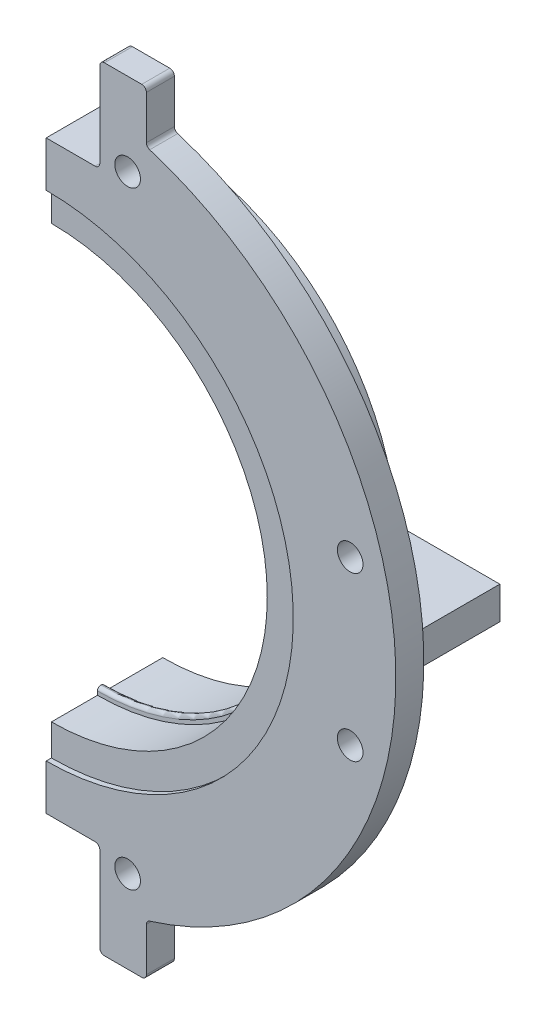
SolidWorks part; units mm, degrees
ref_plane "Front" through (0, 0, 0) normal (0, 0, 1) x (1, 0, 0)
ref_plane "Top" through (0, 0, 0) normal (0, 1, 0) x (1, 0, 0)
ref_plane "Right" through (0, 0, 0) normal (1, 0, 0) x (0, 0, -1)
sketch "Sketch1" plane through (0, 0, 0) normal (0, 0, 1) x (1, 0, 0)
  line L1 (0, 0) -> (180, 0)
  line L2 (0, 0) -> (0, 180)
  line L3 (0, 180) -> (180, 180)
  line L4 (180, 0) -> (180, 180)
  dimension "D1" = 180
extrude "Boss-Extrude1" add sketch "Sketch1" along normal blind 6
sketch "Sketch2" plane through (0, 0, 0) normal (0, 0, -1) x (-1, 0, 0)
  line L0 (0, 90) -> (-180, 90) construction
  line L1 (0, 180) -> (0, 0) construction
  line L3 (-180, 0) -> (-180, 180) construction
  circle A0 centre (-90, 90) radius 46.3
  circle A1 centre (-90, 90) radius 50.3
  point P11 (-90, 90)
  dimension "D1" = 92.6
  dimension "D2" = 4
extrude "Boss-Extrude2" add sketch "Sketch2" along normal blind 19
sketch "Sketch3" plane through (0, 0, 0) normal (0, 0, -1) x (-1, 0, 0)
  circle A0 centre (-90, 90) radius 46.3
  dimension "D1" = 92.6
extrude "Cut-Extrude1" cut sketch "Sketch3" against normal up to next
sketch "Sketch4" plane through (0, 0, 0) normal (0, 0, -1) x (-1, 0, 0)
  line L0 (0, 77.5) -> (0, 102.5)
  line L1 (0, 180) -> (0, 0) construction
  line L2 (0, 77.5) -> (-41.2779, 77.5)
  line L3 (0, 102.5) -> (-41.2779, 102.5)
  circle A0 centre (-90, 90) radius 50.3 construction
  arc A1 (-41.2779, 77.5) -> (-41.2779, 102.5) centre (-90, 90) ccw
  point P2 (0, 90)
  point P5 (0, 90)
  dimension "D1" = 25
extrude "Boss-Extrude3" add sketch "Sketch4" along normal blind 60
ref_plane "Plane1" through (0, 90, 0) normal (0, -1, 0) x (-1, 0, 0)
sketch "Sketch7" plane through (0, 0, 0) normal (0, 0, -1) x (-1, 0, 0)
  circle A0 centre (-90, 90) radius 46.3 construction
  circle A1 centre (-90, 90) radius 46.3 construction
  circle A2 centre (-90, 90) radius 46.3
  circle A3 centre (-90, 90) radius 46.3
sketch "Sketch6" plane through (0, 90, 0) normal (0, -1, 0) x (-1, 0, 0)
  line L0 (-51.2779, -3.75) -> (-40, -3.75)
  line L1 (-40, -3.75) -> (-4, 21.25)
  line L2 (-51.2779, 0.25) -> (-37.2779, 0.25)
  line L3 (-37.2779, 60) -> (-37.2779, 0.25)
  line L4 (-51.2779, 0.25) -> (-51.2779, -3.75)
  line L5 (-4, 21.25) -> (-4, 60)
  line L6 (-41.2779, 60) -> (0, 60) construction
  line L7 (-4, 60) -> (-37.2779, 60)
  line L8 (0, 60) -> (0, 0) construction
  line L9 (-41.2779, 60) -> (-41.2779, 19) construction
  line L10 (-43.7, 19) -> (-136.3, 19) construction
  dimension "D1" = 4
  dimension "D2" = 4
  dimension "D3" = 4
  dimension "D4" = 18.75
  dimension "D5" = 36
  dimension "D6" = 14
  dimension "D7" = 25
extrude "Cut-Extrude2" cut sketch "Sketch6" against normal mid plane 20
fillet "Fillet2" radius 5 2 edges at (4, 90, -21.25) (40, 90, 3.75)
fillet "Fillet3" radius 2 15 edges at (22.4309, 100, -8.4507) (40.0716, 100, 3.5215) (22.4309, 80, -8.4507) (40.0716, 80, 3.5215) (41.0354, 80, -0.25) (41.0354, 100, -0.25) (43.1793, 100, 3.75) (43.1793, 80, 3.75) (4, 100, -41.9326) (4.5694, 100, -21.5478) (4, 80, -41.9326) (4.5694, 80, -21.5478) (37.2779, 100, -30.125) (37.2779, 80, -30.125) (37.2779, 90, -0.25)
fillet "Fillet4" radius 3 2 edges at (41.2779, 77.5, -9.5) (41.2779, 102.5, -9.5)
hole_wizard "M5 Clearance Hole1" positions "Sketch11" profile "Sketch12" hole size "M5" standard "ANSI Metric" end condition up to next
sketch "Sketch11" plane through (0, 0, 0) normal (0, 0, -1) x (-1, 0, 0)
  point P52 (-107.4703, 155.2)
  point P58 (-155.2, 107.4703)
  point P61 (-155.2, 72.5297)
  point P67 (-107.4703, 24.8)
  point P70 (-72.5297, 24.8)
  point P76 (-24.8, 72.5297)
  point P79 (-24.8, 107.4703)
  point P85 (-72.5297, 155.2)
sketch "Sketch12" plane through (107.4703, 155.2, 0) normal (1, 0, 0) x (0, 1, 0)
  line L0 (0, 0) -> (0, 6)
  line L1 (0, 6) -> (2.75, 6)
  line L2 (2.75, 6) -> (2.75, 0)
  line L5 (2.75, 0) -> (0, 0)
  line L11 (0, -6.35) -> (0, 107.95) construction
  dimension "Thru Hole Dia." = 5.5
  dimension "Thru Hole Depth" = 6
sketch "Sketch15" plane through (0, 0, 0) normal (0, 0, -1) x (-1, 0, 0)
  line L0 (-180, 90) -> (-90, 90) construction
  line L3 (-180, 0) -> (-180, 180) construction
  line L4 (-137.3, 93.5) -> (-137.3, 86.5)
  line L5 (-137.3, 93.5) -> (-162.3, 93.5)
  line L6 (-162.3, 93.5) -> (-162.3, 86.5)
  line L7 (-137.3, 86.5) -> (-162.3, 86.5)
  line L8 (-93.5, 42.7) -> (-86.5, 36.7) construction
  line L9 (-93.5, 36.7) -> (-86.5, 42.7) construction
  arc A0 (-41.8739, 104.6276) -> (-41.8739, 75.3724) centre (-90, 90) ccw construction
  point P4 (-137.3, 90)
  point P6 (-90, 39.7)
  dimension "D1" = 7
  dimension "D2" = 25
  dimension "D3" = 47.3
extrude "Boss-Extrude5" add sketch "Sketch15" along normal blind 19
ref_plane "Plane2" through (0, 90, 0) normal (0, 1, 0) x (0, 0, -1)
sketch "Sketch17" plane through (0, 90, 0) normal (0, 1, 0) x (0, 0, -1)
  line L6 (-1.0441, -134.6888) -> (19, -154.733)
  line L8 (19, -140.1781) -> (19, -162.3) construction
  line L9 (19, -154.733) -> (19, -159.233)
  line L10 (19, -159.233) -> (-5.5441, -134.6888)
  line L11 (-5.5441, -134.6888) -> (-1.0441, -134.6888)
  dimension "D1" = 4.5
  dimension "D2" = 4.5
extrude "Cut-Extrude3" cut sketch "Sketch17" against normal mid plane 4 contours L6 L9 L10 | L11 L10 L9 L6 region at (145.8738, 90, -7.8151)
fillet "Fillet5" radius 1.5 4 edges at (145.4949, 92, -9.7619) (145.4949, 88, -9.7619) (147.7449, 92, -7.5119) (147.7449, 88, -7.5119)
sketch "Sketch30" plane through (0, 90, 0) normal (0, -1, 0) x (-1, 0, 0)
  line L1 (22.1625, 78.3225) -> (-206.3555, 78.3225)
  line L2 (22.1625, 78.3225) -> (22.1625, -34.6262)
  line L3 (22.1625, -34.6262) -> (-206.3555, -34.6262)
  line L4 (-206.3555, 78.3225) -> (-206.3555, -34.6262)
sketch "Sketch31" plane through (0, 0, 6) normal (0, 0, 1) x (1, 0, 0)
  line L2 (0, 180) -> (0, 0) construction
  line L3 (0, 0) -> (180, 0) construction
  line L4 (180, 0) -> (180, 180) construction
  line L5 (180, 180) -> (0, 180) construction
  line L8 (0, 180) -> (0, 102.5)
  line L9 (0, 0) -> (180, 0)
  line L10 (180, 0) -> (180, 180)
  line L11 (180, 180) -> (0, 180)
  line L12 (0, 77.5) -> (0, 0)
  line L13 (41.2779, 77.5) -> (0, 77.5) construction
  line L14 (0, 102.5) -> (41.2779, 102.5) construction
  line L15 (16.049, 77.5) -> (0, 77.5)
  line L16 (0, 102.5) -> (16.049, 102.5)
  circle A4 centre (90, 90) radius 75 construction
  arc A5 (16.049, 77.5) -> (16.049, 102.5) centre (90, 90) ccw
extrude "Cut-Extrude4" cut sketch "Sketch31" against normal up to next contours A5 L16 L8 L11 L10 L9 L12 L15
sketch "Sketch33" plane through (0, 0, 6) normal (0, 0, 1) x (1, 0, 0)
  line L1 (0, 102.5) -> (1, 102.5)
  line L2 (0, 102.5) -> (0, 77.5)
  line L3 (0, 77.5) -> (1, 77.5)
  line L4 (1, 102.5) -> (1, 77.5)
  dimension "D1" = 1
extrude "Cut-Extrude5" cut sketch "Sketch33" against normal up to next
sketch "Sketch35" plane through (0, 0, 0) normal (0, 0, -1) x (-1, 0, 0)
  line L0 (-90, 15) -> (-90, 165) construction
  line L4 (-97.5, 152.7377) -> (-82.5, 152.7377)
  line L5 (-97.5, 152.7377) -> (-97.5, 139.7377)
  line L6 (-97.5, 139.7377) -> (-82.5, 139.7377)
  line L7 (-82.5, 152.7377) -> (-82.5, 139.7377)
  line L8 (-97.5, 40.2623) -> (-82.5, 40.2623)
  line L9 (-97.5, 40.2623) -> (-97.5, 27.2623)
  line L10 (-97.5, 27.2623) -> (-82.5, 27.2623)
  line L11 (-82.5, 40.2623) -> (-82.5, 27.2623)
  arc A0 (-16.049, 102.5) -> (-16.049, 77.5) centre (-90, 90) ccw construction
  arc A1 (-41.8739, 104.6276) -> (-140.1781, 93.5) centre (-90, 90) ccw construction
  arc A2 (-140.1781, 86.5) -> (-41.8739, 75.3724) centre (-90, 90) ccw construction
  point P8 (-90, 90)
  point P18 (-90, 152.7377)
  point P26 (-90, 27.2623)
  dimension "D1" = 15
  dimension "D2" = 13
  dimension "D3" = 13
  dimension "D4" = 15
extrude "Boss-Extrude6" add sketch "Sketch35" along normal blind 13
hole_wizard "M5 Clearance Hole2" positions "Sketch38" profile "Sketch39" hole size "M5" standard "ANSI Metric" end condition through all
sketch "Sketch38" plane through (97.5, 0, 0) normal (1, 0, 0) x (0, 0, -1)
  line L0 (13, 152.7377) -> (0, 152.7377) construction
  line L1 (13, 40.2623) -> (13, 27.2623) construction
  line L2 (13, 152.7377) -> (13, 139.7377) construction
  point P0 (6.5, 146.2377)
  point P3 (6.5, 33.7623)
  point P8 (6.5, 152.7377)
  point P12 (13, 33.7623)
  point P15 (13, 146.2377)
sketch "Sketch39" plane through (97.5, 146.2377, -6.5) normal (0, 1, 0) x (0, 0, -1)
  line L0 (0, 0) -> (0, 96.5)
  line L1 (0, 96.5) -> (2.75, 96.5)
  line L2 (2.75, 96.5) -> (2.75, 0)
  line L5 (2.75, 0) -> (0, 0)
  line L11 (0, -6.35) -> (0, 107.95) construction
  dimension "Thru Hole Dia." = 5.5
  dimension "Thru Hole Depth" = 96.5
sketch "Sketch40" plane through (82.5, 0, 0) normal (-1, 0, 0) x (0, 0, 1)
  line L0 (-13, 139.7377) -> (-13, 152.7377) construction
  line L1 (-10.75, 143.784) -> (-6.5, 141.3302)
  line L2 (-6.5, 141.3302) -> (-2.25, 143.784)
  line L3 (-2.25, 143.784) -> (-2.25, 148.6915)
  line L4 (-2.25, 148.6915) -> (-6.5, 151.1452)
  line L5 (-6.5, 151.1452) -> (-10.75, 148.6915)
  line L6 (-10.75, 148.6915) -> (-10.75, 143.784)
  line L7 (-13, 27.2623) -> (-13, 139.7377) construction
  line L8 (-2.25, 31.3085) -> (-2.25, 36.216)
  line L9 (-2.25, 36.216) -> (-6.5, 38.6698)
  line L10 (-6.5, 38.6698) -> (-10.75, 36.216)
  line L11 (-10.75, 36.216) -> (-10.75, 31.3085)
  line L12 (-10.75, 31.3085) -> (-6.5, 28.8548)
  line L13 (-6.5, 28.8548) -> (-2.25, 31.3085)
  circle A0 centre (-6.5, 146.2377) radius 4.25 construction
  circle A1 centre (-6.5, 33.7623) radius 4.25 construction
  dimension "D1" = 8.5
  dimension "D2" = 8.5
extrude "Cut-Extrude6" cut sketch "Sketch40" against normal blind 4.2
sketch "Sketch41" plane through (0, 0, 0) normal (0, 0, -1) x (-1, 0, 0)
  line L0 (-90, 15) -> (-90, 165) construction
  line L2 (22.1625, 90) -> (-206.3555, 90) construction
  line L3 (-101.5, 152.7377) -> (-78.5, 152.7377)
  line L4 (-101.5, 152.7377) -> (-101.5, 167.7377)
  line L5 (-101.5, 167.7377) -> (-78.5, 167.7377)
  line L6 (-78.5, 152.7377) -> (-78.5, 167.7377)
  line L7 (-14.4828, 90) -> (-165.5172, 90) construction
  line L8 (-78.5, 27.2623) -> (-78.5, 12.2623)
  line L9 (-101.5, 12.2623) -> (-78.5, 12.2623)
  line L10 (-101.5, 27.2623) -> (-101.5, 12.2623)
  line L11 (-101.5, 27.2623) -> (-78.5, 27.2623)
  line L14 (-82.5, 152.7377) -> (-97.5, 152.7377) construction
  arc A0 (-16.049, 102.5) -> (-16.049, 77.5) centre (-90, 90) ccw construction
  point P7 (-90, 90)
  point P15 (-90, 152.7377)
  point P24 (-90, 90)
  dimension "D1" = 15
  dimension "D2" = 23
extrude "Cut-Extrude7" cut sketch "Sketch41" against normal up to next
fillet "Fillet8" radius 1 4 edges at (101.5, 164.1131, 3) (78.5, 164.1131, 3) (101.5, 15.8869, 3) (78.5, 15.8869, 3)
sketch "Sketch42" plane through (0, 102.5, 0) normal (0, 1, 0) x (1, 0, 0)
  line L0 (15, -6) -> (1, 24)
  line L1 (165, -6) -> (15, -6) construction
  line L2 (1, -6) -> (16.049, -6) construction
  line L3 (1, 60) -> (1, -6) construction
  line L4 (1, 24) -> (1, -6)
  line L5 (1, -6) -> (15, -6)
  dimension "D1" = 30
  dimension "D2" = 14
extrude "Cut-Extrude8" cut sketch "Sketch42" against normal up to next
ref_plane "Plane3" through (90, 0, 0) normal (1, 0, 0) x (0, 0, -1)
sketch "Sketch43" plane through (90, 0, 0) normal (1, 0, 0) x (0, 0, -1)
  line L1 (-26.2287, 173.6103) -> (66.8607, 173.6103)
  line L2 (-26.2287, 173.6103) -> (-26.2287, 11.2507)
  line L3 (-26.2287, 11.2507) -> (66.8607, 11.2507)
  line L4 (66.8607, 173.6103) -> (66.8607, 11.2507)
sketch "Sketch46" plane through (0, 0, 0) normal (0, 0, -1) x (-1, 0, 0)
  line L0 (-101.5, 162.9366) -> (-101.5, 172.9366)
  line L1 (-101.5, 172.9366) -> (-111.5, 172.9366)
  line L2 (-111.5, 172.9366) -> (-111.5, 161.8523)
  line L9 (-101.5, 152.7377) -> (-101.5, 162.9366)
  line L10 (-101.5, 17.0634) -> (-101.5, 27.2623)
  line L11 (-101.5, 27.2623) -> (-97.5, 27.2623)
  line L12 (-97.5, 27.2623) -> (-97.5, 40.2623)
  line L13 (-140.1781, 86.5) -> (-162.3, 86.5)
  line L14 (-162.3, 86.5) -> (-162.3, 93.5)
  line L15 (-162.3, 93.5) -> (-140.1781, 93.5)
  line L16 (-97.5, 139.7377) -> (-97.5, 152.7377)
  line L17 (-97.5, 152.7377) -> (-101.5, 152.7377)
  line L18 (-101.5, 152.7377) -> (-101.5, 162.9366)
  line L19 (-101.5, 17.0634) -> (-101.5, 27.2623)
  line L20 (-101.5, 27.2623) -> (-97.5, 27.2623)
  line L21 (-97.5, 27.2623) -> (-97.5, 40.2623)
  line L22 (-140.1781, 86.5) -> (-162.3, 86.5)
  line L23 (-162.3, 86.5) -> (-162.3, 93.5)
  line L24 (-162.3, 93.5) -> (-140.1781, 93.5)
  line L25 (-97.5, 139.7377) -> (-97.5, 152.7377)
  line L26 (-97.5, 152.7377) -> (-101.5, 152.7377)
  arc A5 (-101.5, 162.9366) -> (-102.6689, 163.9222) centre (-102.5, 162.9366) ccw
  arc A6 (-102.6689, 163.9222) -> (-102.6689, 16.0778) centre (-90, 90) ccw
  arc A7 (-102.6689, 16.0778) -> (-101.5, 17.0634) centre (-102.5, 17.0634) ccw
  arc A8 (-140.1781, 86.5) -> (-97.5, 40.2623) centre (-90, 90) ccw
  arc A9 (-97.5, 139.7377) -> (-140.1781, 93.5) centre (-90, 90) ccw
  arc A10 (-101.5, 162.9366) -> (-102.6689, 163.9222) centre (-102.5, 162.9366) ccw
  arc A11 (-102.6689, 163.9222) -> (-102.6689, 16.0778) centre (-90, 90) ccw
  arc A12 (-102.6689, 16.0778) -> (-101.5, 17.0634) centre (-102.5, 17.0634) ccw
  arc A13 (-140.1781, 86.5) -> (-97.5, 40.2623) centre (-90, 90) ccw
  arc A14 (-97.5, 139.7377) -> (-140.1781, 93.5) centre (-90, 90) ccw
  arc M18 (-101.5, 162.9366) -> (-102.6689, 163.9222) centre (-102.5, 162.9366) ccw
  arc M19 (-102.6689, 163.9222) -> (-102.6689, 16.0778) centre (-90, 90) ccw
  dimension "D2" = 10
  dimension "D3" = 10
  dimension "D1" = 0
extrude "Boss-Extrude8" add sketch "Sketch46" against normal up to surface (6 mm away) contours L1 L2 L0 M19 M18 region at (106.6758, 167.9846, 0) up to face at (74.0539, 90, 6)
ref_plane "Plane5" through (90, 0, 0) normal (1, 0, 0) x (0, 0, -1)
mirror "Mirror2" about plane through (90, 0, 0) normal (1, 0, 0) of "Boss-Extrude8"
ref_plane "Plane4" through (0, 90, 0) normal (0, 1, 0) x (1, 0, 0)
mirror "Mirror1" about plane through (0, 90, 0) normal (0, 1, 0) of "Mirror2", "Boss-Extrude8"
fillet "Fillet10" radius 1 16 edges at (111.5, 161.8523, 3) (111.5, 172.9366, 3) (101.5, 172.9366, 3) (101.5, 152.7377, 3) (101.5, 27.2623, 3) (101.5, 7.0634, 3) (111.5, 7.0634, 3) (111.5, 18.1477, 3) (68.5, 161.8523, 3) (68.5, 172.9366, 3) (78.5, 152.7377, 3) (78.5, 172.9366, 3) (68.5, 18.1477, 3) (68.5, 7.0634, 3) (78.5, 7.0634, 3) (78.5, 27.2623, 3)
sketch "Sketch47" plane through (0, 0, 6) normal (0, 0, 1) x (1, 0, 0)
  circle A0 centre (90, 90) radius 53
  dimension "D1" = 106
extrude "Cut-Extrude10" cut sketch "Sketch47" against normal blind 1.12
ref_plane "Plane6" through (0, 0, -5) normal (0, 0, 1) x (1, 0, 0)
sketch "Sketch49" plane through (0, 0, -5) normal (0, 0, 1) x (1, 0, 0)
  circle A0 centre (90, 90) radius 46.3
  circle A1 centre (90, 90) radius 44.75
  dimension "D1" = 92.6
  dimension "D2" = 89.5
extrude "Boss-Extrude9" add sketch "Sketch49" against normal blind 1.5
fillet "Fillet11" radius 0.75 2 edges at (134.75, 90, -5) (134.75, 90, -6.5)
sketch "Sketch50" plane through (0, 0, -5) normal (0, 0, 1) x (1, 0, 0)
  line L0 (132.7756, 107.7182) -> (90, 90)
  line L1 (90, 90) -> (132.7756, 72.2818)
  line L2 (162.3, 86.5) -> (140.1781, 86.5) construction
  arc A0 (132.7756, 72.2818) -> (132.7756, 107.7182) centre (90, 90) ccw
  circle A2 centre (90, 90) radius 46.3 construction
  dimension "D1" = 46.3
  dimension "D2" = 45
  dimension "D3" = 22.5
extrude "Cut-Extrude11" [suppressed] cut sketch "Sketch50" against normal up to next
pattern_circular "CirPattern1" [suppressed] count 4 over 360 of bodies 147
fillet "Fillet12" radius 1 6 edges at (44.6367, 80.7339, 0.2018) (44.7016, 80.4217, 2.9784) (44.6367, 99.2661, 3.2982) (44.7016, 99.5783, 0.5216) (43.7, 90, -0.25) (43.7, 90, 3.75)
sketch "Sketch51" plane through (0, 0, -13) normal (0, 0, -1) x (-1, 0, 0)
  line L0 (-82.5, 152.7377) -> (-97.5, 152.7377) construction
  line L1 (60, 190) -> (-90, 190)
  line L2 (60, 190) -> (60, -10)
  line L3 (60, -10) -> (-90, -10)
  line L4 (-90, 190) -> (-90, -10)
  line L5 (-162.3, 93.5) -> (-162.3, 86.5) construction
  point P6 (-90, 152.7377)
  point P7 (-162.3, 90)
  point P10 (-90, 90)
  dimension "D1" = 150
  dimension "D2" = 200
extrude "Cut-Extrude12" cut sketch "Sketch51" against normal through all both and the other way through all
